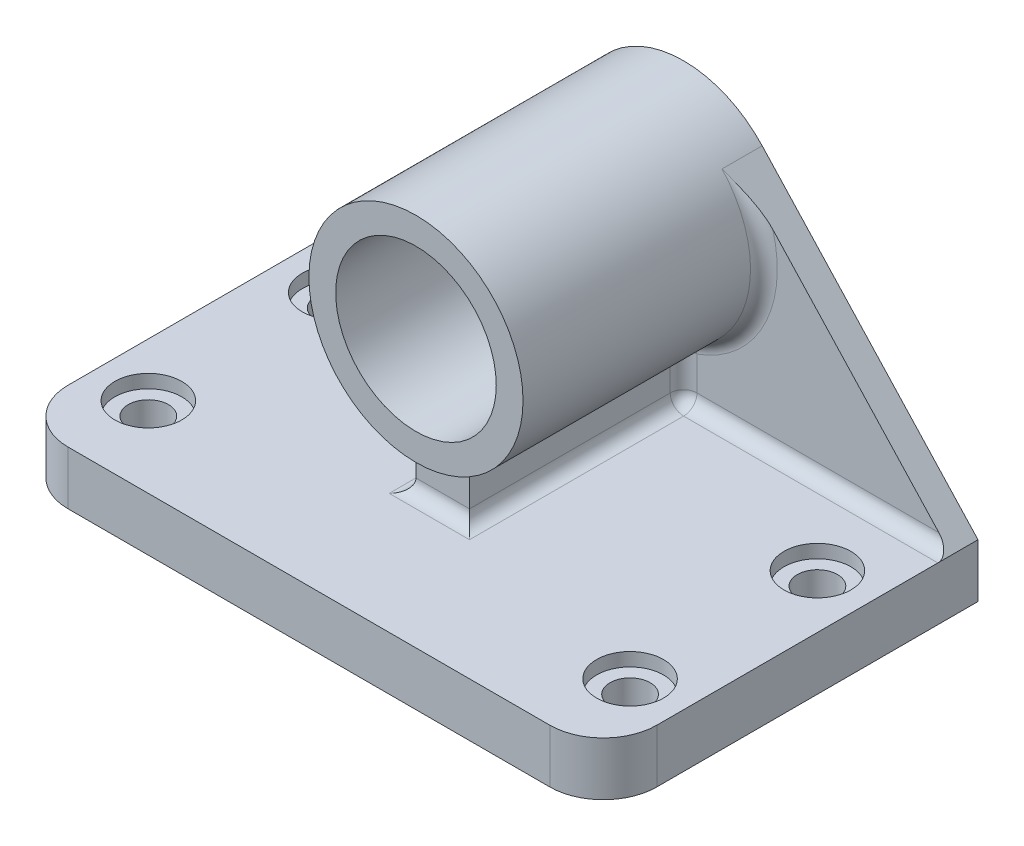
SolidWorks part; units mm, degrees
ref_plane "Front Plane" through (0, 0, 0) normal (0, 0, 1) x (1, 0, 0)
ref_plane "Top Plane" through (0, 0, 0) normal (0, 1, 0) x (1, 0, 0)
ref_plane "Right Plane" through (0, 0, 0) normal (1, 0, 0) x (0, 0, -1)
sketch "Sketch1" plane through (0, 0, 0) normal (1, 0, 0) x (0, 0, -1)
  line L0 (0, 0) -> (-88.9, 0)
  line L1 (0, 0) -> (0, 12.7)
  line L2 (-88.9, 12.7) -> (-88.9, 0)
  line L3 (-88.9, 12.7) -> (0, 12.7)
  dimension "D1" = 12.7
  dimension "D4" = 88.9
extrude "Boss-Extrude1" add sketch "Sketch1" along normal mid plane 139.7 contours L1 L0 L2 L3
sketch "Sketch3" plane through (0, 0, 0) normal (0, 0, -1) x (-1, 0, 0)
  line L0 (-69.85, 0) -> (69.85, 0) construction
  line L1 (0, 50.8) -> (0, 12.7) construction
  line L2 (-69.85, 12.7) -> (69.85, 12.7) construction
  line L3 (-69.85, 12.7) -> (-18.6449, 68.049)
  line L4 (0, 6.985) -> (0, -6.985) construction
  line L5 (69.85, 12.7) -> (18.6449, 68.049)
  line L6 (-69.85, 12.7) -> (69.85, 12.7)
  arc A0 (18.6449, 68.049) -> (-18.6449, 68.049) centre (0, 50.8) ccw
  dimension "D2" = 50.8
  dimension "D1" = 50.8
extrude "Boss-Extrude2" add sketch "Sketch3" against normal blind 6.35
sketch "Sketch4" plane through (0, 0, 6.35) normal (0, 0, 1) x (1, 0, 0)
  line L0 (0, -41.91) -> (0, 41.91) construction
  circle A0 centre (0, 50.8) radius 25.4
  arc A1 (18.6449, 68.049) -> (-18.6449, 68.049) centre (0, 50.8) ccw construction
extrude "Boss-Extrude3" add sketch "Sketch4" along normal blind 57.15
sketch "Sketch5" plane through (0, 0, 63.5) normal (0, 0, 1) x (1, 0, 0)
  circle A0 centre (0, 50.8) radius 19.05
  circle A1 centre (0, 50.8) radius 25.4 construction
  dimension "D1" = 38.1
extrude "Cut-Extrude4" cut sketch "Sketch5" against normal up to next
sketch "Sketch6" plane through (0, 12.7, 0) normal (0, 1, 0) x (1, 0, 0)
  line L1 (-6.35, -6.35) -> (6.35, -6.35)
  line L2 (-6.35, -6.35) -> (-6.35, -57.15)
  line L3 (-6.35, -57.15) -> (6.35, -57.15)
  line L4 (6.35, -6.35) -> (6.35, -57.15)
  line L5 (0, -41.91) -> (0, 41.91) construction
  line L6 (69.85, -6.35) -> (-69.85, -6.35) construction
  point P6 (0, -6.35)
  dimension "D1" = 50.8
  dimension "D2" = 12.7
extrude "Boss-Extrude4" add sketch "Sketch6" along normal up to surface (13.5066 mm away) up to face at (0, 59.4245, 3.175)
sketch "Sketch9" plane through (0, 12.7, 0) normal (0, 1, 0) x (1, 0, 0)
  line L0 (-69.85, -88.9) -> (-69.85, -6.35) construction
  line L1 (-69.85, 0) -> (-18.6449, 0) construction
  line L2 (-69.85, -47.625) -> (69.85, -47.625) construction
  line L3 (69.85, -88.9) -> (69.85, -6.35) construction
  line L4 (0, -41.91) -> (0, 41.91) construction
  circle A0 centre (-57.15, -25.4) radius 7.9375
  circle A1 centre (-57.15, -69.85) radius 7.9375
  circle A2 centre (57.15, -69.85) radius 7.9375
  circle A3 centre (57.15, -25.4) radius 7.9375
  dimension "D3" = 15.875
  dimension "D1" = 12.7
  dimension "D2" = 25.4
extrude "Cut-Extrude5" cut sketch "Sketch9" against normal blind 3.175
sketch "Sketch10" plane through (0, 9.525, 0) normal (0, 1, 0) x (1, 0, 0)
  line L0 (-69.85, -47.625) -> (69.85, -47.625) construction
  line L1 (-69.85, -88.9) -> (-69.85, -6.35) construction
  line L2 (69.85, -88.9) -> (69.85, -6.35) construction
  line L3 (0, -41.91) -> (0, 41.91) construction
  circle A0 centre (-57.15, -25.4) radius 4.7625
  circle A1 centre (-57.15, -25.4) radius 7.9375 construction
  circle A2 centre (-57.15, -69.85) radius 4.7625
  circle A3 centre (57.15, -25.4) radius 4.7625
  circle A4 centre (57.15, -69.85) radius 4.7625
  dimension "D1" = 9.525
extrude "Cut-Extrude6" cut sketch "Sketch10" against normal up to next
fillet "Fillet2" radius 3.175 4 edges at (-6.35, 12.7, 31.75) (-6.35, 26.2066, 31.75) (6.35, 12.7, 31.75) (6.35, 26.2066, 31.75)
fillet "Fillet3" radius 3.175 18 edges at (0, 12.7, 57.15) (0, 25.4, 57.15) (-7.2799, 13.6299, 57.15) (-6.35, 19.8671, 57.15) (-6.9326, 25.6923, 57.15) (7.2799, 13.6299, 57.15) (6.35, 19.8671, 57.15) (6.9326, 25.6923, 57.15) (39.6875, 12.7, 6.35) (7.2799, 13.6299, 6.35) (6.35, 19.8671, 6.35) (6.9326, 25.6923, 6.35) (-39.6875, 12.7, 6.35) (-7.2799, 13.6299, 6.35) (-6.35, 19.8671, 6.35) (-6.9326, 25.6923, 6.35) (24.6585, 44.7077, 6.35) (-24.6585, 44.7077, 6.35)
fillet "Fillet4" radius 12.7 2 edges at (69.85, 6.35, 88.9) (-69.85, 6.35, 88.9)
